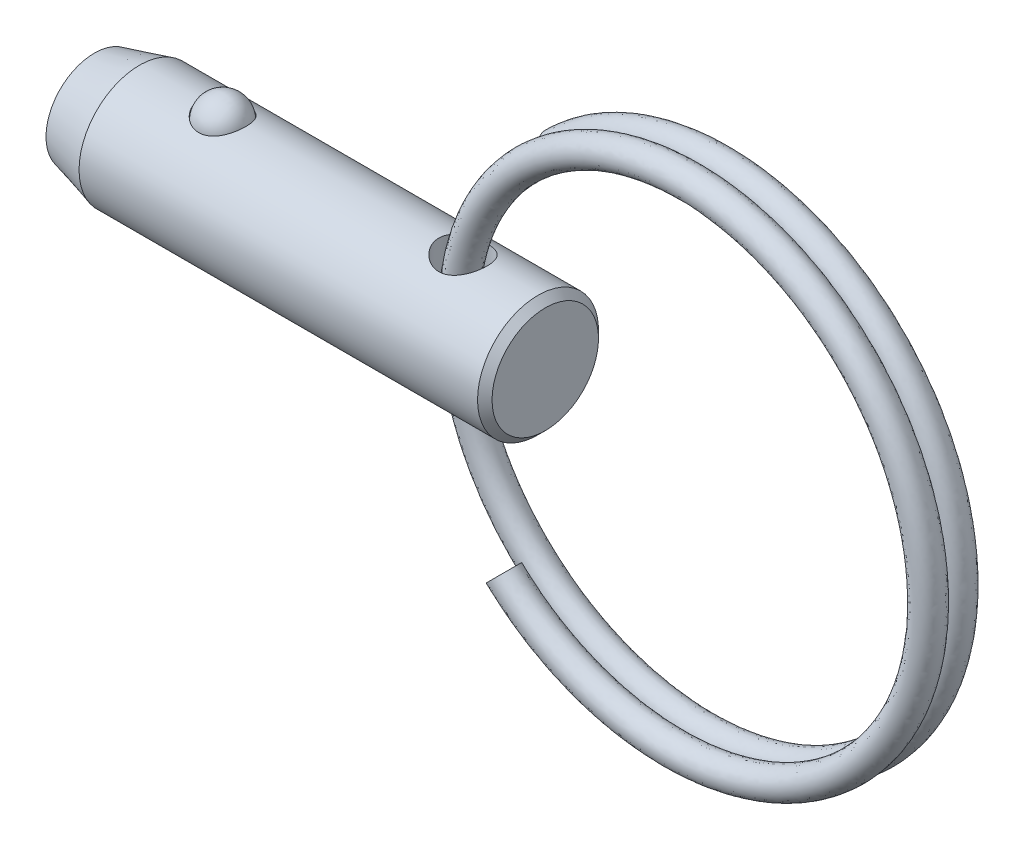
SolidWorks part; units mm, degrees
material "Plain Carbon Steel"
ref_plane "Front" through (0, 0, 0) normal (0, 0, 1) x (1, 0, 0)
ref_plane "Top" through (0, 0, 0) normal (0, 1, 0) x (1, 0, 0)
ref_plane "Right" through (0, 0, 0) normal (1, 0, 0) x (0, 0, -1)
sketch "Sketch1" plane through (0, 0, 0) normal (0, 0, 1) x (1, 0, 0)
  line L0 (11.8364, 2.794) -> (11.4554, 3.175)
  line L1 (11.4554, 3.175) -> (11.8364, 3.175) construction
  line L4 (11.8364, 2.794) -> (11.8364, 0)
  line L5 (11.8364, 3.175) -> (11.8364, 2.794) construction
  line L16 (11.4554, 3.175) -> (-9.4665, 3.175)
  line L17 (-11.8364, 3.175) -> (-11.8364, 2.54) construction
  line L19 (-9.4665, 3.175) -> (-11.8364, 3.175) construction
  line L22 (-11.8364, -3.175) -> (-9.4665, -3.175) construction
  line L23 (-5.1019, 2.8575) -> (-5.1019, -2.8575) construction
  line L24 (-11.8364, 0) -> (11.8364, 0)
  line L27 (11.8364, 0) -> (14.6304, 0) construction
  line L29 (-11.8364, 0) -> (-11.8364, -2.54) construction
  line L36 (6.2484, 0) -> (6.2484, 3.175) construction
  line L37 (-11.8364, 2.54) -> (-11.8364, 0)
  line L38 (-9.4665, -3.175) -> (11.8364, -3.175) construction
  line L39 (-11.8364, -2.54) -> (-11.8364, -3.175) construction
  line L40 (-9.4665, 3.175) -> (-11.8364, 2.54)
  line L42 (-9.4665, -3.175) -> (-11.8364, -2.54) construction
  line L43 (-9.4665, 3.175) -> (-9.4665, -3.175) construction
  circle A2 centre (-5.1019, 2.8575) radius 1.2319 construction
  point P35 (-3.9116, 3.175)
  dimension "A1" = 15
revolve "Revolve1" add sketch "Sketch1" angle 360 about L27
sketch "Sketch2" plane through (0, 0, 0) normal (0, 0, 1) x (1, 0, 0)
  line L0 (-3.8446, 2.8575) -> (-6.3592, 2.8575)
  line L1 (-5.1019, 4.0894) -> (-5.1019, 4.1148) construction
  line L2 (-3.8446, 2.8575) -> (-1.33, 2.8575) construction
  circle A0 centre (-5.1019, 2.8575) radius 1.2319 construction
  circle A1 centre (-5.1019, 2.8575) radius 1.2319 construction
  arc A2 (-6.3592, 2.8575) -> (-3.8446, 2.8575) centre (-5.1019, 2.8575) cw
  dimension "D1" = 0.0254
revolve "Cut-Revolve1" cut sketch "Sketch2" angle 360 about L2
sketch "Sketch3" plane through (0, 0, 0) normal (0, 0, 1) x (1, 0, 0)
  line L0 (-3.87, 2.8575) -> (-6.3338, 2.8575)
  line L1 (-3.87, 2.8575) -> (-1.4062, 2.8575) construction
  circle A0 centre (-5.1019, 2.8575) radius 1.2319 construction
  arc A1 (-3.87, 2.8575) -> (-6.3338, 2.8575) centre (-5.1019, 2.8575) ccw
revolve "Revolve2" add sketch "Sketch3" angle 360 about L1
sketch "Sketch4" plane through (0, 0, 0) normal (0, 0, 1) x (1, 0, 0)
  line L1 (7.5184, -3.175) -> (8.7884, -3.175)
  line L2 (7.5184, -3.175) -> (7.5184, 3.175)
  line L3 (7.5184, 3.175) -> (8.7884, 3.175)
  line L4 (8.7884, -3.175) -> (8.7884, 3.175)
  line L5 (7.5184, -3.175) -> (7.5184, -4.445) construction
  line L6 (8.7884, 3.175) -> (11.8364, 3.175) construction
  line L8 (6.2484, -3.175) -> (6.2484, 3.175) construction
  line L9 (6.2484, 0) -> (7.5184, 0) construction
  line L11 (7.5184, 0) -> (8.7884, 0) construction
  line L12 (11.4554, 3.175) -> (-9.4665, 3.175) construction
  line L14 (-9.4665, -3.175) -> (11.8364, -3.175) construction
  dimension "D1" = 2.54
revolve "Cut-Revolve2" cut sketch "Sketch4" angle 360 about L2
sketch "Sketch5" plane through (0, 0, 0) normal (0, 0, 1) x (1, 0, 0)
  line L0 (0, 0) -> (6.5414, 0) construction
  line L1 (6.5414, 0) -> (6.5414, 3.175) construction
  line L2 (11.4554, 3.175) -> (-9.4665, 3.175) construction
  line L3 (20.0034, 0) -> (33.4654, 0) construction
  line L4 (8.7884, 3.175) -> (8.4954, 3.175) construction
  line L5 (7.5184, 3.175) -> (8.7884, 3.175) construction
  line L6 (6.9212, 3.175) -> (6.9212, -3.175) construction
  line L7 (6.5414, 3.175) -> (6.2484, 3.175) construction
  line L8 (7.5184, -3.175) -> (8.7884, -3.175) construction
  line L9 (6.9212, -3.175) -> (8.7884, -3.175) construction
  line L10 (6.5414, 0) -> (20.0034, 0) construction
  line L12 (8.4954, 3.175) -> (6.9212, 3.175) construction
  line L13 (20.0034, 11.938) -> (20.0034, 13.462) construction
  circle A0 centre (20.0034, 0) radius 13.462
  circle A1 centre (20.0034, 0) radius 11.938 construction
  circle A2 centre (20.0034, 0) radius 12.7 construction
  point P26 (20.0034, 12.7)
curve "Helix/Spiral1" pitch 1.5494 height 1.3557 radius 13.462 left hand yes centre (20.0034, 0, 0) axis (0, 0, -1) start towards (1, 0, 0)
sketch "Sketch6" plane through (114.0038, 0, 0) normal (0, 1, 0) x (0, 0, -1)
  line L0 (0, 105.9384) -> (0, 106.7004) construction
  line L1 (0, 106.7004) -> (0, 107.4624) construction
  circle A0 centre (0, 106.7004) radius 0.762
  dimension "D1" = 1.524
sketch "Sketch7" plane through (0, 0, 0) normal (0, 0, 1) x (1, 0, 0)
  circle A0 centre (20.0034, 0) radius 13.462 construction
  circle A1 centre (20.0034, 0) radius 13.462
curve "Helix/Spiral2" pitch 1.5494 height 1.3557 radius 13.462 left hand yes centre (20.0034, 0, 0) axis (0, 0, 1) start towards (1, 0, 0)
sweep "Sweep1" add profiles "Sketch6" path "Helix/Spiral1"
sweep "Sweep2" add profiles "Sketch6<2>" path "Helix/Spiral2"
sketch "Sketch6<2>" plane through (114.0038, 0, 0) normal (0, 1, 0) x (0, 0, -1) same geometry as "Sketch6"
equation "\"D12@Sketch1\"=\"A@Sketch1\" * 0.80"
equation "\"D2@Sketch1\"=\"A@Sketch1\" * 0.9"
equation "\"D1@Sketch4\" = \"A@Sketch1\" / 2.5"
equation "\"Ring OD@Sketch5\" = \"R Ring Dia@Sketch5\" * 0.06"
equation "\"D4@Helix/Spiral1\"=\"Ring OD@Sketch5\" + 0.001"
equation "\"D1@Sketch6\"=\"Ring OD@Sketch5\""
equation "\"D4@Helix/Spiral2\" = \"D4@Helix/Spiral1\""
equation "\"D5@Helix/Spiral2\" = \"D5@Helix/Spiral1\""
